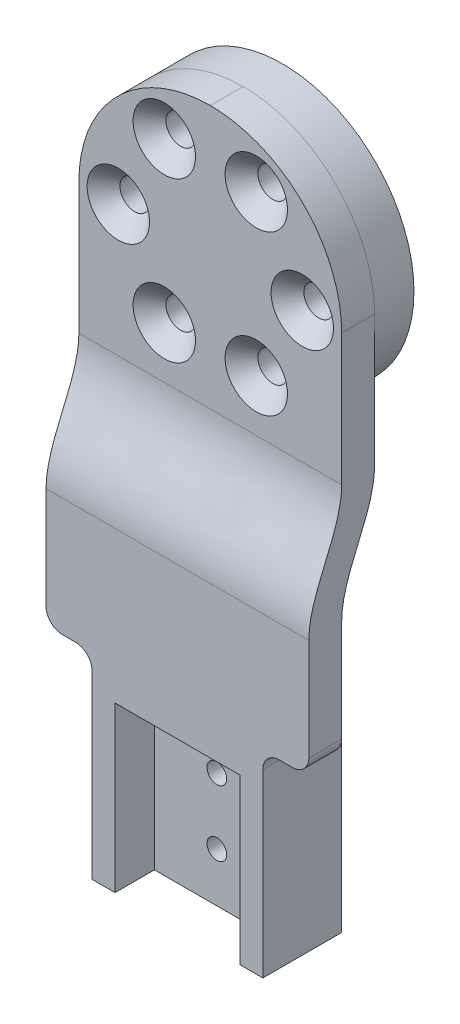
SolidWorks part; units mm, degrees
other "Markup1"
sketch "Sketch13" plane through (20, -53, 11) normal (0.0614, -0.6805, 0.7302) x (0.9699, -0.1321, -0.2046)
sketch "Sketch23" plane through (20.0001, -86, 16.0001) normal (0.0614, -0.6805, 0.7302) x (0.9699, -0.1321, -0.2046)
ref_plane "Front Plane" through (0, 0, 0) normal (0, 0, 1) x (1, 0, 0)
ref_plane "Top Plane" through (0, 0, 0) normal (0, 1, 0) x (1, 0, 0)
ref_plane "Right Plane" through (0, 0, 0) normal (1, 0, 0) x (0, 0, -1)
sketch "Sketch7" plane through (0, 0, 0) normal (0, 0, 1) x (1, 0, 0)
  line L1 (-20, 20) -> (20, 20)
  line L2 (-20, 20) -> (-20, -20)
  line L3 (-20, -20) -> (20, -20)
  line L4 (20, 20) -> (20, -20)
  line L5 (-20, 20) -> (20, -20) construction
  line L6 (-20, -20) -> (20, 20) construction
  point P0 (0, 0)
extrude "Boss-Extrude1" add sketch "Sketch7" along normal blind 11
ref_plane "Plane2" through (0, -21.4103, 5.7369) normal (0, -0.9659, 0.2588) x (1, 0, 0)
sketch "Sketch8" plane through (0, -20, 2.0782) normal (0, -1, 0) x (1, 0, 0)
  line L0 (20, 8.9218) -> (20, -2.0782) construction
  line L1 (-20, 8.9218) -> (20, 8.9218)
  line L2 (-20, 8.9218) -> (-20, 3.9218)
  line L3 (-20, 3.9218) -> (20, 3.9218)
  line L4 (20, 8.9218) -> (20, 3.9218)
  line L5 (0, 3.9218) -> (0, 8.9218) construction
  line L6 (-20, 6.4218) -> (20, 6.4218) construction
  line L7 (-20, -2.0782) -> (20, -2.0782) construction
  point P764 (0, 6.4218)
  dimension "D1" = 6
ref_plane "Plane4" through (0, -38, 0) normal (0, -1, 0) x (-1, 0, 0)
sketch "Sketch19" plane through (0, -38, 0) normal (0, -1, 0) x (-1, 0, 0)
  line L0 (20, -11) -> (20, 0) construction
  line L1 (20, -16) -> (-20, -16)
  line L2 (20, -16) -> (20, -11)
  line L3 (20, -11) -> (-20, -11)
  line L4 (-20, -16) -> (-20, -11)
  line L5 (20, -16) -> (-20, -11) construction
  line L6 (20, -11) -> (-20, -16) construction
  line L7 (-20, -11) -> (-20, 0) construction
  line L8 (20, -11) -> (-20, -11) construction
  point P4 (0, -13.5)
  dimension "D1" = 5
  dimension "D2" = 5
loft "Loft1" add profiles "Sketch19", "Sketch8" start constraint normal to profile start tangent length 1 end constraint normal to profile end tangent length 1 connector at (-20, -38, 16) connector at (-20, -20, 11)
sketch "Sketch16" plane through (0, 0, 0) normal (0, 0, -1) x (-1, 0, 0)
  line L1 (24.5131, 32.6211) -> (-24.5131, 32.6211)
  line L2 (24.5131, 32.6211) -> (24.5131, -32.6211)
  line L3 (24.5131, -32.6211) -> (-24.5131, -32.6211)
  line L4 (-24.5131, 32.6211) -> (-24.5131, -32.6211)
  line L5 (24.5131, 32.6211) -> (-24.5131, -32.6211) construction
  line L6 (24.5131, -32.6211) -> (-24.5131, 32.6211) construction
  circle A0 centre (0, 0) radius 20
extrude "Cut-Extrude3" cut sketch "Sketch16" against normal blind 6
ref_plane "Plane3" [suppressed] through (0, -56, 0) normal (0, -1, 0) x (-1, 0, 0)
sketch "Sketch17" plane through (0, -38, 0) normal (0, -1, 0) x (-1, 0, 0)
  line L1 (20, -16) -> (-20, -16)
  line L2 (20, -16) -> (20, -11)
  line L3 (20, -11) -> (-20, -11)
  line L4 (-20, -16) -> (-20, -11)
  line L5 (20, -16) -> (-20, -11) construction
  line L6 (20, -11) -> (-20, -16) construction
  line L10 (-20, -16) -> (20, -16) construction
  line L11 (-20, -6) -> (-20, -11) construction
  line L12 (20, -11) -> (20, -6) construction
  point P4 (0, -13.5)
  dimension "D1" = 5
extrude "Boss-Extrude5" add sketch "Sketch17" along normal blind 18
sketch "Sketch10" plane through (0, 0, 11) normal (0, 0, 1) x (1, 0, 0)
  circle A0 centre (-7.0001, 12.1244) radius 2.25
  circle A1 centre (6.9999, 12.1244) radius 2.25
  circle A2 centre (13.9999, 0.0001) radius 2.25
  circle A3 centre (6.9999, -12.1243) radius 2.25
  circle A4 centre (-7.0001, -12.1243) radius 2.25
  circle A5 centre (-14.0001, 0.0001) radius 2.25
  point P0 (0, 0)
  point P1 (0.0025, 0.0011)
  dimension "D4" = 4.5
extrude "Cut-Extrude1" cut sketch "Sketch10" against normal blind 25
sketch "Sketch11" plane through (0, -56, -3.473) normal (0, 1, 0) x (1, 0, 0)
  line L0 (20, -19.473) -> (-20, -19.473) construction
  line L5 (13, -7.473) -> (-13, -7.473)
  line L6 (13, -7.473) -> (13, -19.473)
  line L7 (13, -19.473) -> (-13, -19.473)
  line L8 (-13, -7.473) -> (-13, -19.473)
  line L9 (13, -7.473) -> (-13, -19.473) construction
  line L10 (13, -19.473) -> (-13, -7.473) construction
  line L12 (-20, -19.473) -> (-20, -14.473) construction
  point P0 (0, -13.473)
  dimension "D1" = 26
  dimension "D2" = 20
  dimension "D3" = 12
chamfer "Chamfer1" distance 2.5 angle 45 6 edges at (-4.7501, 12.1244, 11) (-11.7501, 0.0001, 11) (-4.7501, -12.1243, 11) (9.2499, 12.1244, 11) (16.2499, 0.0001, 11) (9.2499, -12.1243, 11)
fillet "Fillet3" radius 20 2 edges at (20, 20, 8.5) (-20, 20, 8.5)
extrude "Boss-Extrude6" add sketch "Sketch11" against normal blind 30
ref_plane "Plane5" through (0, -86, 0) normal (0, -1, 0) x (-1, 0, 0)
sketch "Sketch21" plane through (0, -86, 0) normal (0, -1, 0) x (-1, 0, 0)
  line L0 (13, -16) -> (-13, -16) construction
  line L1 (-9.5, -10) -> (9.5, -10)
  line L2 (-9.5, -10) -> (-9.5, -16)
  line L3 (-9.5, -16) -> (9.5, -16)
  line L4 (9.5, -10) -> (9.5, -16)
  line L5 (-9.5, -10) -> (9.5, -16) construction
  line L6 (-9.5, -16) -> (9.5, -10) construction
  line L7 (13, -4) -> (13, -16) construction
  point P0 (0, -13)
  dimension "D1" = 6
  dimension "D2" = 19
  dimension "D3" = 13
extrude "Cut-Extrude4" cut sketch "Sketch21" against normal blind 25
fillet "Fillet5" radius 2.5 4 edges at (-13, -56, 13.5) (-20, -56, 13.5) (13, -56, 13.5) (20, -56, 13.5)
fillet "Fillet7" radius 2.5 2 edges at (0, -56, 11) (0, -56, 4)
sketch "Sketch22" plane through (0, 0, 0) normal (0, 0, 1) x (1, 0, 0)
  line L0 (13, -86) -> (13, -58.5) construction
  line L1 (-17.6217, -73.5) -> (22.5957, -73.5) construction
  line L2 (-6.6, -86) -> (6.6, -86) construction
  circle A0 centre (0, -68.5) radius 1.5
  circle A1 centre (0, -78.5) radius 1.5
  dimension "D1" = 3
  dimension "D2" = 3
  dimension "D3" = 10
  dimension "D4" = 13
  dimension "D5" = 5
  dimension "D6" = 12.5
extrude "Cut-Extrude5" cut sketch "Sketch22" against normal mid plane 25
